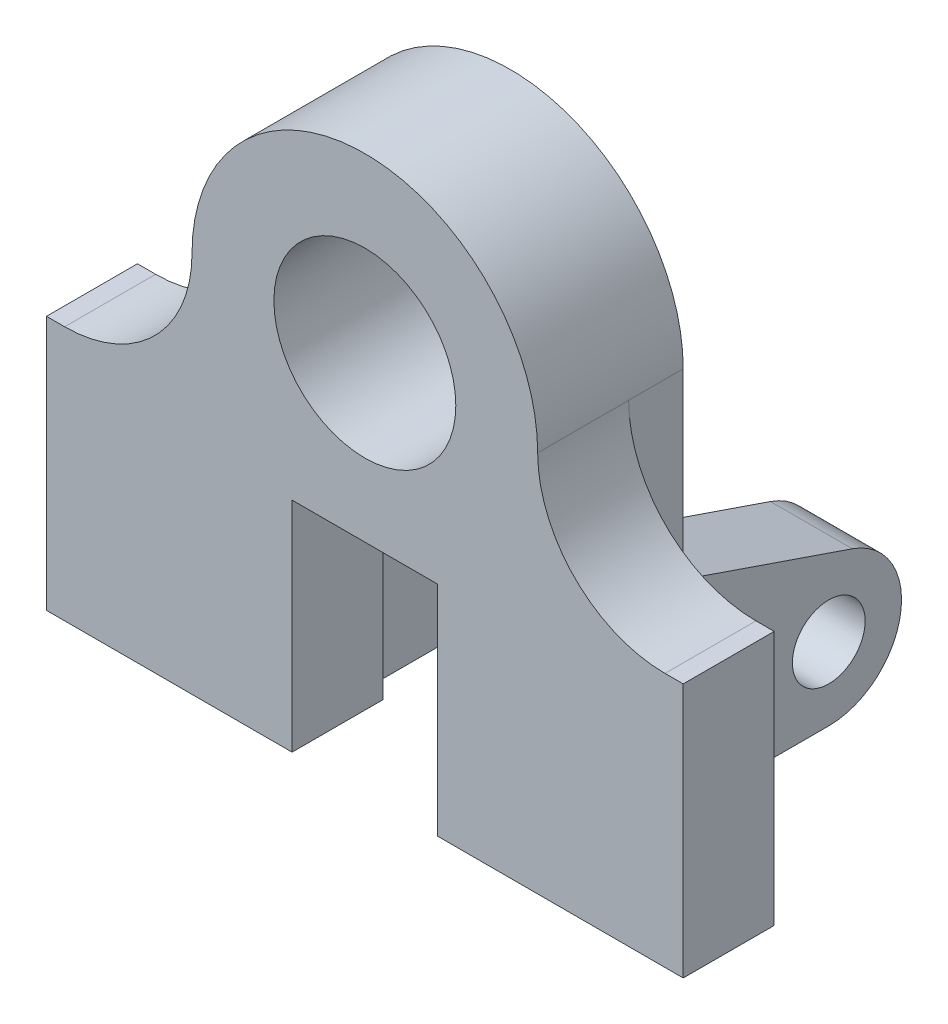
SolidWorks part; units mm, degrees
ref_plane "Front Plane" through (0, 0, 0) normal (0, 0, 1) x (1, 0, 0)
ref_plane "Top Plane" through (0, 0, 0) normal (0, 1, 0) x (1, 0, 0)
ref_plane "Right Plane" through (0, 0, 0) normal (1, 0, 0) x (0, 0, -1)
sketch "Sketch2" plane through (0, 0, 0) normal (0, 0, 1) x (1, 0, 0)
  line L0 (0, 0) -> (32, 0)
  line L1 (32, 0) -> (32, 28)
  line L2 (108, 28) -> (108, 0)
  line L3 (108, 0) -> (140, 0)
  line L4 (140, 0) -> (140, -56)
  line L5 (140, -56) -> (108, -56)
  line L6 (108, -56) -> (108, -8)
  line L7 (108, -8) -> (89.3384, -8)
  line L8 (89.3384, -8) -> (32, -8)
  line L9 (32, -8) -> (32, -56)
  line L10 (32, -56) -> (0, -56)
  line L11 (0, -56) -> (0, 0)
  line L12 (108, 0) -> (106.1638, 1.7991)
  arc A0 (32, 28) -> (108, 28) centre (70, 28) cw
  dimension "D1" = 38
  dimension "D2" = 32
  dimension "D3" = 32
  dimension "D4" = 56
  dimension "D5" = 48
  dimension "D6" = 76
  dimension "D7" = 28
extrude "Boss-Extrude2" add sketch "Sketch2" along normal mid plane 20
fillet "Fillet3" radius 28 2 edges at (32, 0, 0) (108, 0, 0)
sketch "Sketch4" plane through (0, 0, 10) normal (0, 0, 1) x (1, 0, 0)
  line L0 (108, -56) -> (90, -56)
  line L1 (90, -56) -> (90, -8)
  line L2 (108, -8) -> (32, -8) construction
  line L3 (90, -8) -> (86, -8)
  line L4 (86, -8) -> (86, -56)
  line L5 (86, -56) -> (90, -56)
  line L6 (32, -56) -> (50, -56)
  line L7 (50, -56) -> (50, -8)
  line L8 (50, -8) -> (54, -8)
  line L9 (54, -8) -> (54, -56)
  line L10 (54, -56) -> (50, -56)
  line M10 (32, -56) -> (32, -8)
  line M11 (32, -8) -> (108, -8)
  line M12 (108, -8) -> (108, -56)
  dimension "D1" = 18
  dimension "D2" = 18
  dimension "D3" = 4
  dimension "D4" = 4
extrude "Boss-Extrude4" add sketch "Sketch4" against normal through all contours L1 L0 M12 M11 | L4 L5 L1 M11 | L6 L7 M11 M10
sketch "Sketch9" plane through (0, 0, -10) normal (0, 0, -1) x (-1, 0, 0)
  line L0 (-86, -8) -> (-90, -8)
  line L1 (-90, -8) -> (-90, -56)
  line L2 (-140, -56) -> (-86, -56) construction
  line L3 (-90, -56) -> (-108, -56)
  line L4 (-108, -56) -> (-108, -8)
  line L5 (-108, -8) -> (-90, -8)
  line L6 (-108, -56) -> (-90, -56)
  line L7 (-90, -8) -> (-108, -8)
  line M11 (-140, -56) -> (-86, -56)
  dimension "D1" = 18
  dimension "D2" = 4
extrude "Boss-Extrude6" add sketch "Sketch9" along normal blind 60 contours L5 L4 L1 M11
sketch "Sketch10" plane through (108, 0, 0) normal (1, 0, 0) x (0, 0, -1)
  line L0 (10, -8) -> (59.1892, -24.8649)
  line L3 (70, -56) -> (10, -56) construction
  line L4 (54, -56) -> (54, -40)
  circle A0 centre (54, -40) radius 16
extrude "Cut-Extrude2" cut sketch "Sketch10" against normal blind 60 contours A0 L3 L4 L0 | A0 L0 L3
sketch "Sketch12" plane through (0, 0, -10) normal (0, 0, -1) x (-1, 0, 0)
  line L0 (-54, -8) -> (-50, -8)
  line L1 (-50, -8) -> (-50, -56)
  line L2 (-54, -56) -> (0, -56) construction
  line L3 (-50, -56) -> (-32, -56)
  line L4 (-32, -56) -> (-32, -8)
  line L5 (-32, -8) -> (-50, -8)
  line M8 (-54, -56) -> (0, -56)
  dimension "D1" = 4
  dimension "D2" = 18
extrude "Boss-Extrude7" add sketch "Sketch12" along normal blind 60 contours L4 L5 L1 M8
sketch "Sketch13" plane through (32, 0, 0) normal (-1, 0, 0) x (0, 0, 1)
  line L0 (-70, -56) -> (-54, -56)
  line L1 (-70, -56) -> (-10, -56) construction
  line L2 (-54, -56) -> (-54, -40)
  line L3 (-10, -8) -> (-59.1892, -24.8649)
  circle A0 centre (-54, -40) radius 16
  line M3 (-10, -8) -> (-70, -8)
  line M4 (-70, -8) -> (-70, -56)
  line M5 (-70, -56) -> (-10, -56)
extrude "Cut-Extrude3" cut sketch "Sketch13" against normal blind 60 contours A0 L3 M3 M4 | A0 M4 M5
sketch "Sketch14" plane through (108, 0, 0) normal (1, 0, 0) x (0, 0, -1)
  circle A0 centre (54, -40) radius 8
  dimension "D1" = 16
extrude "Cut-Extrude4" cut sketch "Sketch14" against normal blind 140
sketch "Sketch15" plane through (0, 0, -10) normal (0, 0, -1) x (-1, 0, 0)
  circle A0 centre (-70, 28) radius 20
  dimension "D1" = 40
extrude "Cut-Extrude5" cut sketch "Sketch15" against normal blind 140
sketch "Sketch18" plane through (0, 0, -10) normal (0, 0, -1) x (-1, 0, 0)
  line L0 (-108, 28) -> (-108, -8)
  line L1 (-108, -8) -> (-32, -8)
  line L2 (-32, -8) -> (-32, 28)
  arc A0 (-32, 28) -> (-108, 28) centre (-70, 28) ccw
  circle A1 centre (-70, 28) radius 20
extrude "Boss-Extrude9" add sketch "Sketch18" along normal blind 12
